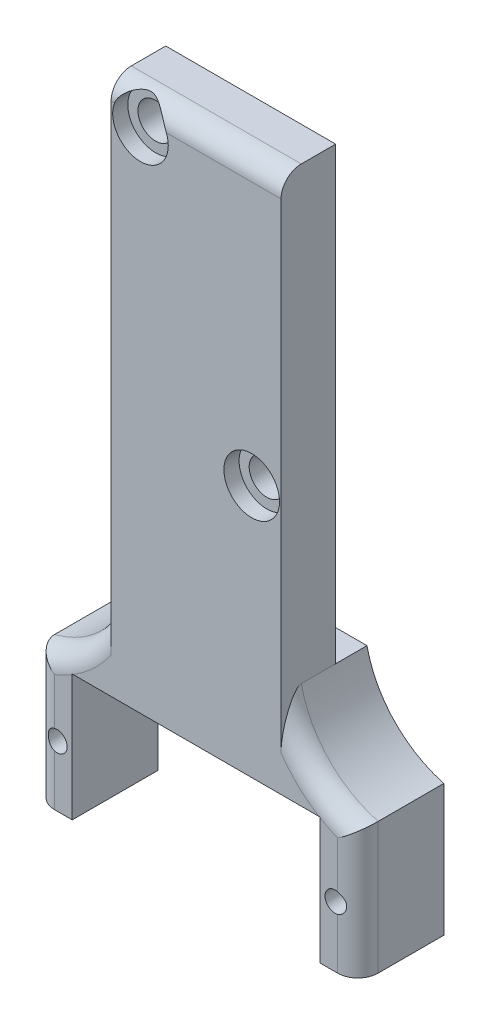
SolidWorks part; units mm, degrees
ref_plane "Alzado" through (0, 0, 0) normal (0, 0, 1) x (1, 0, 0)
ref_plane "Planta" through (0, 0, 0) normal (0, 1, 0) x (1, 0, 0)
ref_plane "Vista lateral" through (0, 0, 0) normal (1, 0, 0) x (0, 0, -1)
sketch "Croquis2" plane through (0, 33.2825, 0) normal (0, 1, 0) x (1, 0, 0)
  line L0 (2.7644, 0) -> (2.7644, -1) construction
  line L2 (19.7644, -1) -> (19.7644, 0) construction
  line L3 (2.7644, 0) -> (2.7644, -1) construction
  line L5 (19.7644, -1) -> (19.7644, 0) construction
  line L6 (19.6644, -1) -> (19.6644, -0.1)
  line L7 (19.6644, -0.1) -> (2.8644, -0.1)
  line L8 (2.8644, -0.1) -> (2.8644, -1)
  line L10 (2.7644, -3) -> (-2.7512, -3) construction
  line L11 (2.7644, -3) -> (-2.7512, -3) construction
  line L12 (2.8644, -1) -> (2.8644, -3)
  line L13 (19.6644, -1) -> (19.6644, -3)
  line L14 (19.6644, -3) -> (2.8644, -3)
  line L15 (19.7644, 0) -> (2.7644, 0) construction
  dimension "D1" = 16.8
extrude "Saliente-Extruir1" add sketch "Croquis2" against normal up to surface (52.5 mm away)
sketch "Croquis3" plane through (0, 0, 3) normal (0, 0, 1) x (1, 0, 0)
  circle A0 centre (5.7644, 30.2825) radius 1.45 construction
  circle A1 centre (16.7644, 5.2825) radius 1.45 construction
  circle A2 centre (5.7644, 30.2825) radius 1.45 construction
  circle A3 centre (16.7644, 5.2825) radius 1.45 construction
  circle A4 centre (5.7644, 30.2825) radius 1.75
  circle A5 centre (16.7644, 5.2825) radius 1.75
  dimension "D1" = 3.5
  dimension "D2" = 3.5
extrude "Cortar-Extruir3" cut sketch "Croquis3" against normal up to next
sketch "Croquis4" plane through (0, 0, 3) normal (0, 0, 1) x (1, 0, 0)
  circle A0 centre (5.7644, 30.2825) radius 2.75
  circle A1 centre (16.7644, 5.2825) radius 2.75
  dimension "D1" = 5.5
  dimension "D2" = 5.5
extrude "Cortar-Extruir4" cut sketch "Croquis4" against normal blind 1.5
sketch "Croquis5" plane through (0, 0, 0) normal (0, 0, 1) x (1, 0, 0)
  line L1 (2.8644, -19.2175) -> (19.6644, -19.2175)
  line L3 (2.8644, -32.2175) -> (19.6644, -32.2175)
  line L5 (19.6644, -19.2175) -> (27.2644, -19.2175)
  line L7 (19.6644, -32.2175) -> (27.2644, -32.2175)
  line L8 (27.2644, -19.2175) -> (27.2644, -32.2175)
  line L9 (2.8644, -19.2175) -> (-4.7356, -19.2175)
  line L11 (2.8644, -32.2175) -> (-4.7356, -32.2175)
  line L12 (-4.7356, -19.2175) -> (-4.7356, -32.2175)
  dimension "D1" = 13
  dimension "D2" = 32
extrude "Saliente-Extruir2" add sketch "Croquis5" along normal blind 3
sketch "Croquis6" plane through (0, 0, 3) normal (0, 0, 1) x (1, 0, 0)
  line L0 (-4.7356, -32.2175) -> (27.2644, -32.2175) construction
  line L1 (-0.9856, -32.2175) -> (23.5144, -32.2175)
  line L2 (-0.9856, -32.2175) -> (-0.9856, -19.7175)
  line L3 (-0.9856, -19.7175) -> (23.5144, -19.7175)
  line L4 (23.5144, -32.2175) -> (23.5144, -19.7175)
  line L5 (-4.7356, -19.2175) -> (-4.7356, -32.2175) construction
  line L6 (27.2644, -32.2175) -> (27.2644, -19.2175) construction
  circle A0 centre (-2.4856, -26.2175) radius 1
  circle A1 centre (25.0144, -26.2175) radius 1
  dimension "D5" = 2
  dimension "D1" = 24.5
  dimension "D2" = 12.5
  dimension "D3" = 3.75
  dimension "D4" = 3.75
  dimension "D6" = 1.5
  dimension "D7" = 6.5
extrude "Cortar-Extruir5" cut sketch "Croquis6" against normal blind 12.9 and the other way blind 7
sketch "Croquis7" plane through (0, 0, 0) normal (0, 0, -1) x (-1, 0, 0)
  line L0 (-19.6644, -19.2175) -> (-19.6644, 33.2825) construction
  line L3 (-27.2644, -19.2175) -> (-19.6644, -19.2175)
  line L4 (-19.6644, -19.2175) -> (-19.6644, -11.2175)
  line L5 (-2.8644, -19.2175) -> (-2.8644, -11.2175)
  line L6 (4.7356, -19.2175) -> (-2.8644, -19.2175)
  arc A0 (-27.2644, -19.2175) -> (-19.6644, -11.2175) centre (-29.9939, -9.0145) ccw
  arc A1 (4.7356, -19.2175) -> (-2.8644, -11.2175) centre (7.4651, -9.0145) cw
  dimension "D1" = 8
  dimension "D2" = 8
extrude "Saliente-Extruir3" add sketch "Croquis7" against normal blind 3
sketch "Croquis11" plane through (0, 0, 3) normal (0, 0, 1) x (1, 0, 0)
  line L10 (2.8644, 33.2825) -> (2.8644, -11.2175)
  line L11 (-4.7356, -19.2175) -> (-4.7356, -32.2175)
  line L12 (-4.7356, -32.2175) -> (-0.9856, -32.2175)
  line L14 (-0.9856, -32.2175) -> (-0.9856, -19.7175)
  line L15 (-0.9856, -32.2175) -> (-0.9856, -19.7175)
  line L16 (-0.9856, -19.7175) -> (23.5144, -19.7175)
  line L17 (27.2644, -32.2175) -> (27.2644, -19.2175)
  line L18 (19.6644, -11.2175) -> (19.6644, 33.2825)
  line L19 (19.6644, 33.2825) -> (2.8644, 33.2825)
  line L20 (-0.9856, -19.7175) -> (23.5144, -19.7175)
  line L21 (-4.7356, -19.2175) -> (-4.7356, -32.2175)
  line L22 (-4.7356, -32.2175) -> (-0.9856, -32.2175)
  line L23 (23.5144, -19.7175) -> (23.5144, -32.2175)
  line L24 (23.5144, -19.7175) -> (23.5144, -32.2175)
  line L25 (23.5144, -32.2175) -> (27.2644, -32.2175)
  line L26 (23.5144, -32.2175) -> (27.2644, -32.2175)
  line L27 (27.2644, -32.2175) -> (27.2644, -19.2175)
  arc A2 (-4.7356, -19.2175) -> (2.8644, -11.2175) centre (-7.4651, -9.0145) ccw
  arc A3 (19.6644, -11.2175) -> (27.2644, -19.2175) centre (29.9939, -9.0145) ccw
  arc A4 (-4.7356, -19.2175) -> (2.8644, -11.2175) centre (-7.4651, -9.0145) ccw
  arc A5 (19.6644, -11.2175) -> (27.2644, -19.2175) centre (29.9939, -9.0145) ccw
  dimension "D1" = 0
sketch "Croquis17" plane through (0, 0, 0) normal (0, 0, -1) x (-1, 0, 0)
  line L0 (-19.6644, -11.2175) -> (-2.8644, -11.2175)
  line L10 (0.9856, -19.7175) -> (0.9856, -32.2175)
  line L11 (0.9856, -32.2175) -> (4.7356, -32.2175)
  line L12 (4.7356, -32.2175) -> (4.7356, -19.2175)
  line L13 (-2.8644, -11.2175) -> (-2.8644, -19.2175)
  line L14 (-2.8644, -19.2175) -> (-19.6644, -19.2175)
  line L15 (-19.6644, -19.2175) -> (-19.6644, -11.2175)
  line L16 (-27.2644, -19.2175) -> (-27.2644, -32.2175)
  line L17 (-27.2644, -32.2175) -> (-23.5144, -32.2175)
  line L18 (-23.5144, -32.2175) -> (-23.5144, -19.7175)
  line L19 (-23.5144, -19.7175) -> (0.9856, -19.7175)
  line L20 (0.9856, -19.7175) -> (0.9856, -32.2175)
  line L21 (0.9856, -32.2175) -> (4.7356, -32.2175)
  line L22 (4.7356, -32.2175) -> (4.7356, -19.2175)
  line L26 (-27.2644, -19.2175) -> (-27.2644, -32.2175)
  line L27 (-27.2644, -32.2175) -> (-23.5144, -32.2175)
  line L28 (-23.5144, -32.2175) -> (-23.5144, -19.7175)
  line L29 (-23.5144, -19.7175) -> (0.9856, -19.7175)
  arc A2 (-2.8644, -11.2175) -> (4.7356, -19.2175) centre (7.4651, -9.0145) ccw
  arc A3 (-27.2644, -19.2175) -> (-19.6644, -11.2175) centre (-29.9939, -9.0145) ccw
  arc A4 (-2.8644, -11.2175) -> (4.7356, -19.2175) centre (7.4651, -9.0145) ccw
  arc A5 (-27.2644, -19.2175) -> (-19.6644, -11.2175) centre (-29.9939, -9.0145) ccw
  dimension "D1" = 0
extrude "Saliente-Extruir4" add sketch "Croquis17" along normal blind 3
sketch "Croquis16" plane through (0, 0, 3) normal (0, 0, 1) x (1, 0, 0)
  circle A0 centre (-2.4856, -26.2175) radius 1 construction
  circle A1 centre (25.0144, -26.2175) radius 1 construction
  circle A2 centre (-2.4856, -26.2175) radius 1
  circle A3 centre (25.0144, -26.2175) radius 1
extrude "Cortar-Extruir6" cut sketch "Croquis16" against normal blind 14
sketch "Croquis18" plane through (0, 0, 3) normal (0, 0, 1) x (1, 0, 0)
  line L10 (2.8644, 33.2825) -> (2.8644, -11.2175)
  line L11 (-4.7356, -19.2175) -> (-4.7356, -32.2175)
  line L12 (-4.7356, -32.2175) -> (-0.9856, -32.2175)
  line L13 (-0.9856, -32.2175) -> (-0.9856, -19.7175)
  line L14 (-0.9856, -19.7175) -> (23.5144, -19.7175)
  line L15 (23.5144, -19.7175) -> (23.5144, -32.2175)
  line L16 (23.5144, -32.2175) -> (27.2644, -32.2175)
  line L17 (27.2644, -32.2175) -> (27.2644, -19.2175)
  line L18 (19.6644, -11.2175) -> (19.6644, 33.2825)
  line L19 (19.6644, 33.2825) -> (2.8644, 33.2825)
  line L20 (2.8644, 33.2825) -> (2.8644, -11.2175)
  line L21 (-4.7356, -19.2175) -> (-4.7356, -32.2175)
  line L22 (-4.7356, -32.2175) -> (-0.9856, -32.2175)
  line L23 (-0.9856, -32.2175) -> (-0.9856, -19.7175)
  line L24 (-0.9856, -19.7175) -> (23.5144, -19.7175)
  line L25 (23.5144, -19.7175) -> (23.5144, -32.2175)
  line L26 (23.5144, -32.2175) -> (27.2644, -32.2175)
  line L27 (27.2644, -32.2175) -> (27.2644, -19.2175)
  line L28 (19.6644, -11.2175) -> (19.6644, 33.2825)
  line L29 (19.6644, 33.2825) -> (2.8644, 33.2825)
  circle A0 centre (5.7644, 30.2825) radius 2.75 construction
  circle A1 centre (5.7644, 30.2825) radius 2.75
  arc A2 (-4.7356, -19.2175) -> (2.8644, -11.2175) centre (-7.4651, -9.0145) ccw
  arc A3 (19.6644, -11.2175) -> (27.2644, -19.2175) centre (29.9939, -9.0145) ccw
  arc A4 (-4.7356, -19.2175) -> (2.8644, -11.2175) centre (-7.4651, -9.0145) ccw
  arc A5 (19.6644, -11.2175) -> (27.2644, -19.2175) centre (29.9939, -9.0145) ccw
  circle A6 centre (16.7644, 5.2825) radius 2.75 construction
  circle A7 centre (16.7644, 5.2825) radius 2.75
  circle A8 centre (-2.4856, -26.2175) radius 1 construction
  circle A9 centre (-2.4856, -26.2175) radius 1
  circle A10 centre (25.0144, -26.2175) radius 1 construction
  circle A11 centre (25.0144, -26.2175) radius 1
  dimension "D1" = 0
extrude "Saliente-Extruir5" add sketch "Croquis18" along normal blind 2.5
sketch "Croquis19" plane through (0, 0, 1.5) normal (0, 0, 1) x (1, 0, 0)
  circle A0 centre (5.7644, 30.2825) radius 1.75 construction
  circle A1 centre (5.7644, 30.2825) radius 2.75
  circle A2 centre (5.7644, 30.2825) radius 2.75
  circle A3 centre (5.7644, 30.2825) radius 1.75
  dimension "D1" = 0
extrude "Saliente-Extruir6" add sketch "Croquis19" along normal blind 2.5
sketch "Croquis20" plane through (0, 0, 1.5) normal (0, 0, 1) x (1, 0, 0)
  circle A0 centre (16.7644, 5.2825) radius 1.75 construction
  circle A1 centre (16.7644, 5.2825) radius 2.75
  circle A2 centre (16.7644, 5.2825) radius 2.75
  circle A3 centre (16.7644, 5.2825) radius 1.75
  dimension "D1" = 0
extrude "Saliente-Extruir7" add sketch "Croquis20" along normal blind 2.5
fillet "Redondeo1" radius 2 5 edges at (-4.7356, -25.7175, 5.5) (0.1922, -16.2889, 5.5) (22.3366, -16.2889, 5.5) (27.2644, -25.7175, 5.5) (11.2644, 33.2825, 5.5)
equation "\"D2@Croquis3\"= \"D1@Croquis3\""
equation "\"D2@Croquis4\"= \"D1@Croquis4\""
